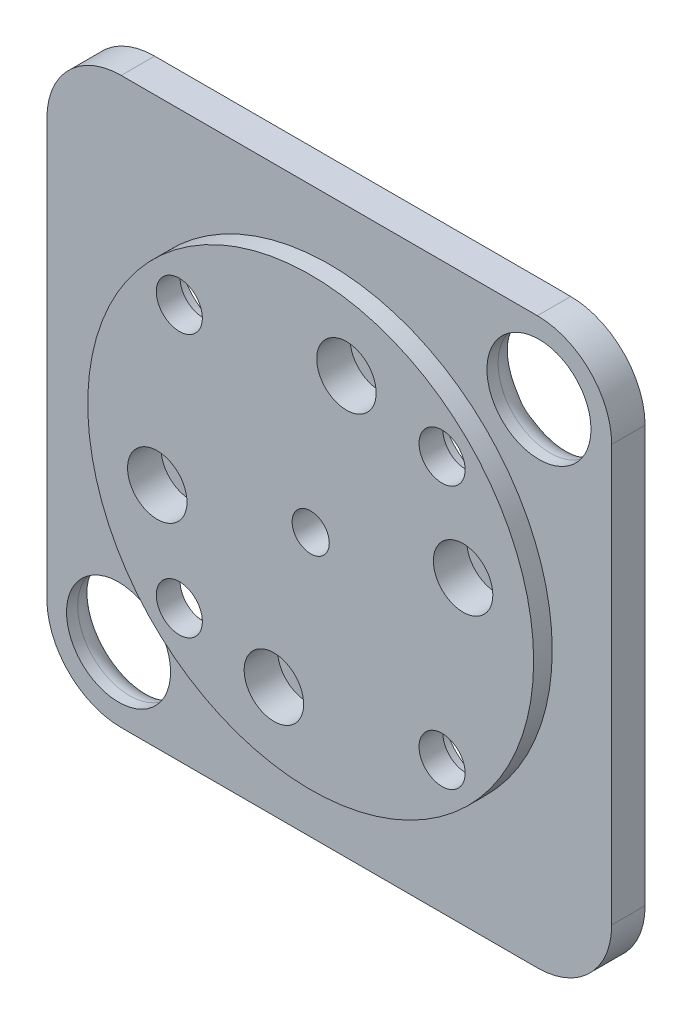
SolidWorks part; units mm, degrees
ref_plane "Front Plane" through (0, 0, 0) normal (0, 0, 1) x (1, 0, 0)
ref_plane "Top Plane" through (0, 0, 0) normal (0, 1, 0) x (1, 0, 0)
ref_plane "Right Plane" through (0, 0, 0) normal (1, 0, 0) x (0, 0, -1)
sketch "Sketch1" plane through (0, 0, 0) normal (0, 0, 1) x (1, 0, 0)
  line L1 (0, 0) -> (76, 0)
  line L2 (0, 0) -> (0, 76)
  line L3 (0, 76) -> (76, 76)
  line L4 (76, 0) -> (76, 76)
  dimension "D1" = 76
  dimension "D2" = 76
extrude "Boss-Extrude1" add sketch "Sketch1" along normal blind 4.5
sketch "Sketch2" plane through (0, 0, 4.5) normal (0, 0, 1) x (1, 0, 0)
  line L0 (0, 38) -> (76, 38) construction
  line L1 (0, 76) -> (0, 0) construction
  line L2 (76, 0) -> (76, 76) construction
  line L3 (26.8, 56) -> (26.8, 20) construction
  line L4 (49, 56) -> (49, 20) construction
  line L5 (26.8, 56) -> (49, 56) construction
  line L6 (55.6777, 55.6777) -> (20.3223, 20.3223) construction
  line L7 (20.3223, 55.6777) -> (55.6777, 20.3223) construction
  line L8 (37.9, 78) -> (37.9, -2) construction
  circle A0 centre (26.8, 56) radius 1.575 construction
  circle A1 centre (49, 56) radius 1.575 construction
  circle A2 centre (26.8, 20) radius 1.575 construction
  circle A3 centre (49, 20) radius 1.575 construction
  circle A4 centre (38, 38) radius 25 construction
  circle A5 centre (55.6777, 55.6777) radius 3.1
  circle A6 centre (20.3223, 55.6777) radius 3.1
  circle A7 centre (20.3223, 20.3223) radius 3.1
  circle A8 centre (55.6777, 20.3223) radius 3.1
  circle A9 centre (37.9, 78) radius 7 construction
  circle A10 centre (37.9, -2) radius 7 construction
  circle A11 centre (13, 38) radius 3.1 construction
  circle A12 centre (63, 38) radius 3.1 construction
  circle A13 centre (38, 38) radius 2.5
  circle A14 centre (66.2136, 66.355) radius 7
  circle A15 centre (42.8083, 58.6475) radius 1.575
  circle A16 centre (58.5061, 42.9497) radius 1.575
  circle A17 centre (17.3525, 33.1917) radius 1.575
  circle A18 centre (9.645, 9.7864) radius 7
  circle A19 centre (33.0503, 17.4939) radius 1.575
  point P18 (38, 38)
  point P29 (37.9, 38)
  point P30 (37.9, 56)
  point P36 (32, 38)
  point P52 (38, 38)
  dimension "D1" = 3.15
  dimension "D2" = 22.2
  dimension "D3" = 22.2
  dimension "D4" = 18
  dimension "D5" = 18
  dimension "D7" = 50
  dimension "D10" = 6.2
  dimension "D11" = 14
  dimension "D13" = 2
  dimension "D15" = 5
  dimension "D6" = 27
  dimension "D8" = 45
  dimension "D9" = 45
  dimension "D12" = 80
extrude "Cut-Extrude1" cut sketch "Sketch2" against normal through all
fillet "Fillet1" radius 10 4 edges at (76, 0, 2.25) (76, 76, 2.25) (0, 0, 2.25) (0, 76, 2.25)
sketch "Sketch3" plane through (0, 0, 0) normal (0, 0, -1) x (-1, 0, 0)
  circle A0 centre (-55.6777, 55.6777) radius 7.25
  circle A1 centre (-20.3223, 55.6777) radius 7.25
  circle A2 centre (-55.6777, 20.3223) radius 7.25
  circle A3 centre (-20.3223, 20.3223) radius 7.25
  dimension "D1" = 14.5
extrude "Cut-Extrude2" cut sketch "Sketch3" against normal blind 3.8
sketch "Sketch4" plane through (0, 0, 4.5) normal (0, 0, 1) x (1, 0, 0)
  circle A0 centre (58.5061, 42.9497) radius 4
  circle A1 centre (33.0503, 17.4939) radius 4
  circle A2 centre (17.3525, 33.1917) radius 4
  circle A3 centre (42.8083, 58.6475) radius 4
  dimension "D1" = 8
extrude "Cut-Extrude3" cut sketch "Sketch4" against normal blind 2
fillet "Fillet2" radius 3 2 edges at (73.2136, 66.355, 0) (16.645, 9.7864, 0)
sketch "Sketch6" plane through (0, 0, 4.5) normal (0, 0, 1) x (1, 0, 0)
  circle A6 centre (38, 38) radius 2.5
  circle A9 centre (58.5061, 42.9497) radius 4 construction
  circle A10 centre (55.6777, 55.6777) radius 3.1
  circle A11 centre (55.6777, 20.3223) radius 3.1
  circle A12 centre (38, 38) radius 2.5 construction
  circle A14 centre (20.3223, 55.6777) radius 3.1
  circle A20 centre (38, 38) radius 30
  circle A22 centre (58.5061, 42.9497) radius 4
  circle A23 centre (42.8083, 58.6475) radius 4
  circle A24 centre (33.0503, 17.4939) radius 4
  circle A25 centre (17.3525, 33.1917) radius 4
  circle A27 centre (20.3223, 20.3223) radius 3.1
  dimension "D1" = 60
  dimension "D2" = 6.2
extrude "Boss-Extrude2" add sketch "Sketch6" along normal blind 2.5
